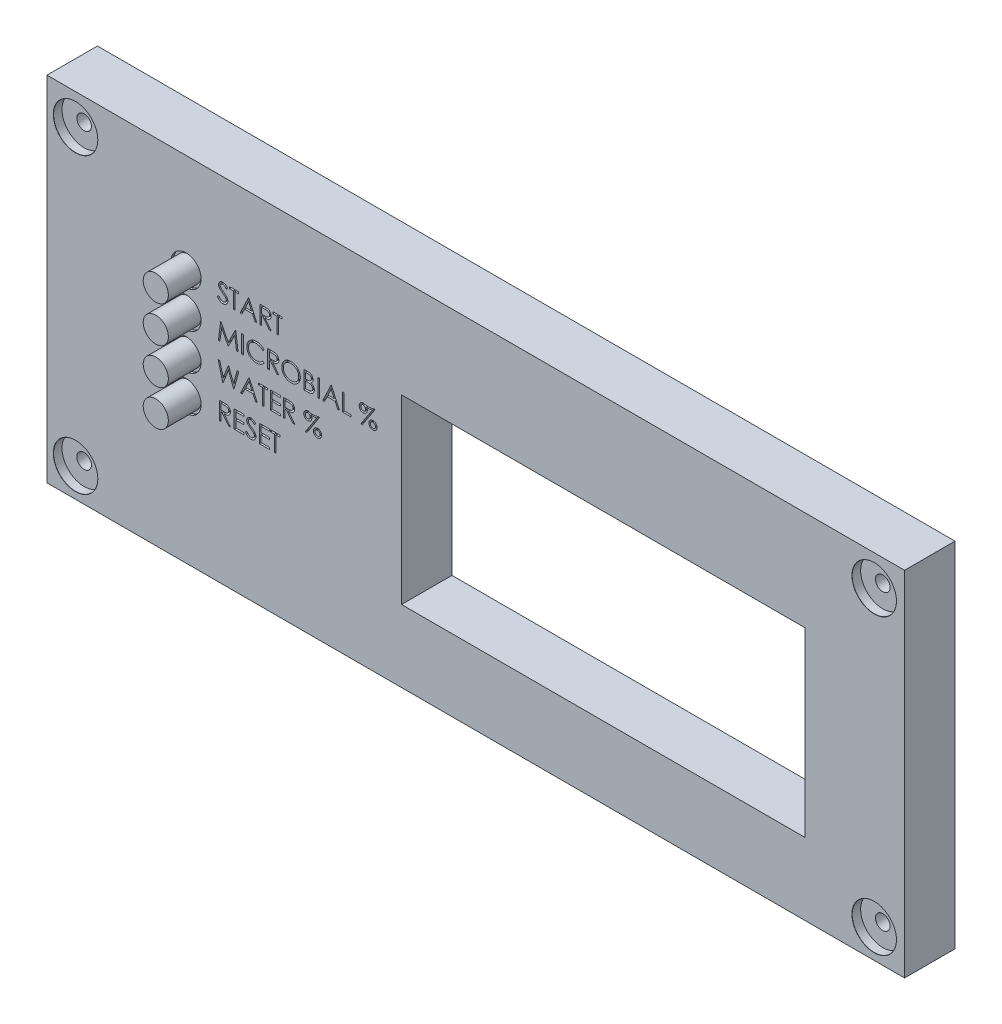
SolidWorks part; units mm, degrees
ref_plane "Front Plane" through (0, 0, 0) normal (0, 0, 1) x (1, 0, 0)
ref_plane "Top Plane" through (0, 0, 0) normal (0, 1, 0) x (1, 0, 0)
ref_plane "Right Plane" through (0, 0, 0) normal (1, 0, 0) x (0, 0, -1)
sketch "Sketch1" plane through (0, 0, 0) normal (0, 0, 1) x (1, 0, 0)
  line L1 (-85, -35) -> (85, -35)
  line L2 (-85, -35) -> (-85, 35)
  line L3 (-85, 35) -> (85, 35)
  line L4 (85, -35) -> (85, 35)
  line L5 (-85, -35) -> (85, 35) construction
  line L6 (-85, 35) -> (85, -35) construction
  point P0 (0, 0)
  dimension "D1" = 170
  dimension "D2" = 70
extrude "Boss-Extrude1" add sketch "Sketch1" along normal blind 10
sketch "Sketch2" plane through (0, 0, 10) normal (0, 0, 1) x (1, 0, 0)
  line L1 (65.2812, -20.7427) -> (-14.7188, -20.7427)
  line L2 (65.2812, -20.7427) -> (65.2812, 15.2573)
  line L3 (65.2812, 15.2573) -> (-14.7188, 15.2573)
  line L4 (-14.7188, -20.7427) -> (-14.7188, 15.2573)
  dimension "D1" = 80
  dimension "D2" = 36
extrude "Cut-Extrude1" cut sketch "Sketch2" against normal blind 10
hole_wizard "CBORE for M2.5 Hex Head Cap Screw1" positions "Sketch3" profile "Sketch4" counterbore size "M2.5" standard "ISO" end condition through all
sketch "Sketch3" plane through (0, 0, 10) normal (0, 0, 1) x (1, 0, 0)
  point P0 (-79.3377, 28.899)
  point P2 (-79.3377, -29.258)
  point P4 (78.9787, -29.258)
  point P6 (78.9787, 28.899)
sketch "Sketch4" plane through (-79.3377, 28.899, 10) normal (1, 0, 0) x (0, -1, 0)
  line L0 (0, 0) -> (0, 10)
  line L1 (0, 10) -> (1.45, 10)
  line L3 (1.45, 10) -> (1.45, 1.7)
  line L4 (4.387, 1.7) -> (1.45, 1.7)
  line L5 (4.387, 1.7) -> (4.387, 0.025)
  line L6 (4.387, 0.025) -> (4.412, 0)
  line L7 (4.412, 0) -> (0, 0)
  line L8 (-4.387, 0.025) -> (-4.412, 0) construction
  line L11 (0, -6.35) -> (0, 107.95) construction
  dimension "Thru Hole Dia." = 2.9
  dimension "Thru Hole Depth" = 10
  dimension "C'Bore Dia." = 8.774
  dimension "C'Bore Depth" = 1.7
  dimension "Near C'Sink Dia." = 8.824
  dimension "Near C'Sink Angle" = 90
sketch "Sketch5" plane through (0, 0, 10) normal (0, 0, 1) x (1, 0, 0)
  circle A0 centre (-57.4346, -6.2823) radius 2.4898
  circle A1 centre (-57.4346, 0.9077) radius 2.4898
  circle A2 centre (-57.4346, 8.1004) radius 2.4898
  circle A3 centre (-57.4346, 0.9077) radius 2.9898
  circle A4 centre (-57.4346, 8.1004) radius 2.9898
  circle A5 centre (-57.4346, -6.2823) radius 2.9898
  circle A6 centre (-57.4346, 15.2903) radius 2.4898
  circle A7 centre (-57.4346, 15.2903) radius 2.9898
  dimension "D1" = 7.1927
  dimension "D2" = 7.1898
extrude "Boss-Extrude4" add sketch "Sketch5" along normal blind 6 contours A2 | A1 | A0 | A6
extrude "Cut-Extrude3" cut sketch "Sketch5<4>" against normal blind 0.5
sketch "Sketch5<4>" plane through (0, 0, 10) normal (0, 0, 1) x (1, 0, 0) same geometry as "Sketch5"
sketch "Sketch10" plane through (0, 0, 10) normal (0, 0, 1) x (1, 0, 0)
  text T0 "START\r\nMICROBIAL %\r\nWATER %\r\nRESET"
extrude "Cut-Extrude4" cut sketch "Sketch10" against normal blind 1
